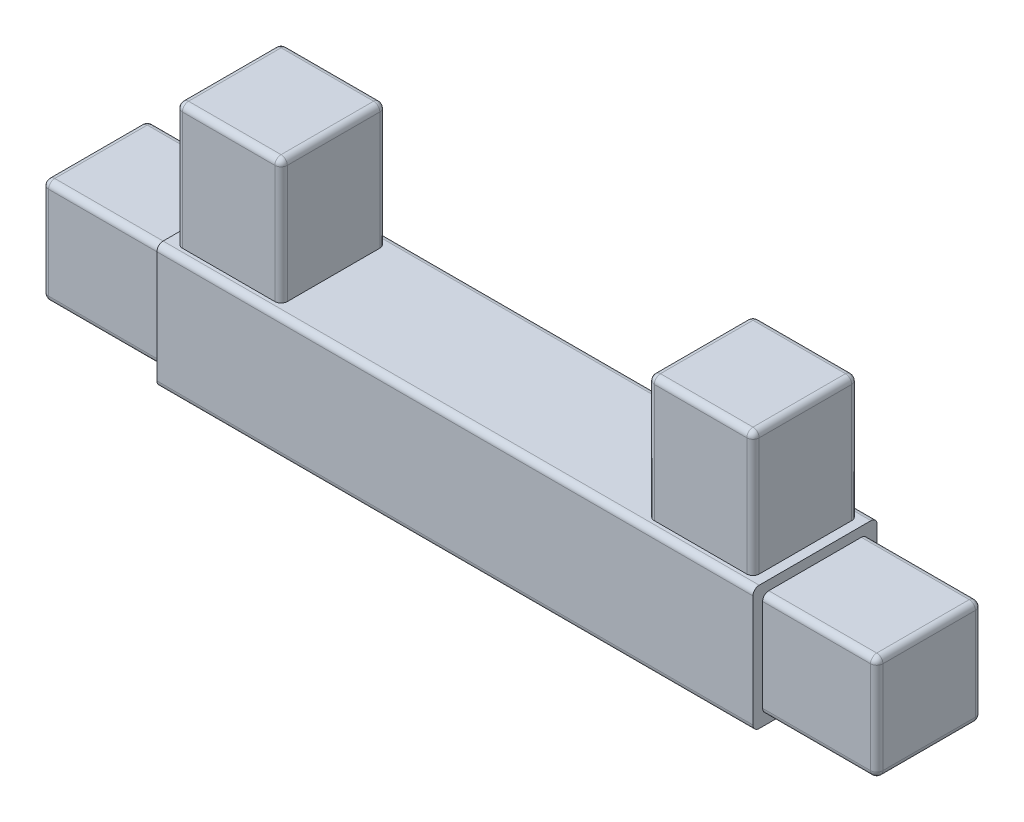
SolidWorks part; units mm, degrees
ref_plane "Front Plane" through (0, 0, 0) normal (0, 0, 1) x (1, 0, 0)
ref_plane "Top Plane" through (0, 0, 0) normal (0, 1, 0) x (1, 0, 0)
ref_plane "Right Plane" through (0, 0, 0) normal (1, 0, 0) x (0, 0, -1)
sketch "Sketch1" plane through (0, 0, 0) normal (0, 1, 0) x (1, 0, 0)
  line L0 (-68, 0) -> (-48, 0) construction
  line L1 (-28, -10) -> (28, -10)
  line L2 (-28, -10) -> (-28, 10)
  line L3 (-28, 10) -> (28, 10)
  line L4 (28, -10) -> (28, 10)
  line L5 (-28, -10) -> (28, 10) construction
  line L6 (-28, 10) -> (28, -10) construction
  line L7 (-28, -10) -> (-48, -10)
  line L8 (-28, -10) -> (-28, 10)
  line L9 (-28, 10) -> (-48, 10)
  line L10 (-48, -10) -> (-48, 10)
  line L11 (28, -10) -> (48, -10)
  line L12 (28, -10) -> (28, 10)
  line L13 (28, 10) -> (48, 10)
  line L14 (48, -10) -> (48, 10)
  line L15 (48, -8.45) -> (66.3784, -8.45)
  line L16 (48, -8.45) -> (48, 8.45)
  line L17 (48, 8.45) -> (66.3784, 8.45)
  line L18 (66.3784, -8.45) -> (66.3784, 8.45)
  line L19 (-48, -8.45) -> (-68, -8.45)
  line L20 (-48, -8.45) -> (-48, 8.45)
  line L21 (-48, 8.45) -> (-68, 8.45)
  line L22 (-68, -8.45) -> (-68, 8.45)
  point P0 (0, 0)
  point P20 (66.3784, 0)
  dimension "D1" = 20
  dimension "D2" = 16.9
  dimension "D3" = 20
  dimension "D4" = 56
  dimension "D5" = 20
  dimension "D6" = 20
extrude "Boss-Extrude1" add sketch "Sketch1" along normal blind 20 contours L10 L7 L2 L9 | L1 L4 L3 L2 | L11 L14 L13 L4 region at (0, 0, 0) region at (-38, 0, 0) region at (38, 0, 0)
extrude "Boss-Extrude2" add sketch "Sketch1<3>" along normal blind 16.9 from offset 1.55 contours L22 L19 L10 L21 | L15 L18 L17 L14 region at (-58, 0, 0) region at (57.1892, 0, 0)
sketch "Sketch1<3>" plane through (0, 0, 0) normal (0, 1, 0) x (1, 0, 0) same geometry as "Sketch1"
sketch "Sketch2" plane through (0, 20, 0) normal (0, 1, 0) x (1, 0, 0)
  line L9 (0, -9.0234) -> (0, 7.4527) construction
  line L10 (46.45, -8.45) -> (29.55, -8.45)
  line L11 (46.45, 8.45) -> (46.45, -8.45)
  line L12 (29.55, 8.45) -> (46.45, 8.45)
  line L13 (-46.45, -8.45) -> (-29.55, -8.45)
  line L14 (-46.45, 8.45) -> (-46.45, -8.45)
  line L15 (-29.55, -8.45) -> (-29.55, 8.45)
  line L16 (-29.55, 8.45) -> (-46.45, 8.45)
  line L17 (-46.45, -8.45) -> (-29.55, -8.45)
  line L18 (-46.45, 8.45) -> (-46.45, -8.45)
  line L19 (-29.55, -8.45) -> (-29.55, 8.45)
  line L20 (-29.55, 8.45) -> (-46.45, 8.45)
  line L21 (29.55, -8.45) -> (29.55, 8.45)
  dimension "D1" = 1.55
extrude "Boss-Extrude3" add sketch "Sketch2" along normal blind 20
fillet "Fillet2" radius 1 36 edges at (-58, 18.45, 8.45) (-46.45, 30, 8.45) (-46.45, 30, -8.45) (-38, 40, -8.45) (-46.45, 40, 0) (-38, 40, 8.45) (-29.55, 40, 0) (-29.55, 30, 8.45) (-29.55, 30, -8.45) (29.55, 30, -8.45) (29.55, 30, 8.45) (38, 40, -8.45) (29.55, 40, 0) (38, 40, 8.45) (46.45, 40, 0) (46.45, 30, -8.45) (46.45, 30, 8.45) (57.1892, 1.55, -8.45) (0, 0, -10) (57.1892, 18.45, -8.45) (66.3784, 10, -8.45) (66.3784, 18.45, 0) (66.3784, 10, 8.45) (57.1892, 1.55, 8.45) (66.3784, 1.55, 0) (57.1892, 18.45, 8.45) (0, 20, -10) (0, 0, 10) (0, 20, 10) (-58, 1.55, -8.45) (-68, 1.55, 0) (-58, 1.55, 8.45) (-68, 10, -8.45) (-58, 18.45, -8.45) (-68, 18.45, 0) (-68, 10, 8.45)
